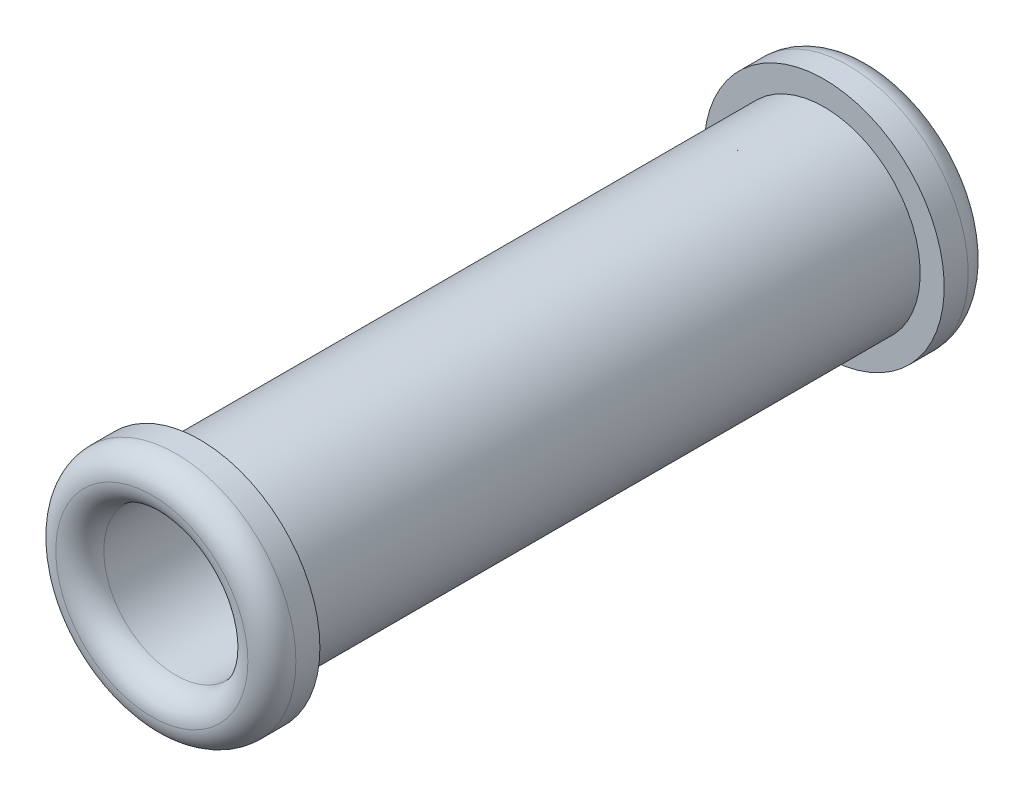
SolidWorks part; units mm, degrees
ref_plane "Front Plane" through (0, 0, 0) normal (0, 0, 1) x (1, 0, 0)
ref_plane "Top Plane" through (0, 0, 0) normal (0, 1, 0) x (1, 0, 0)
ref_plane "Right Plane" through (0, 0, 0) normal (1, 0, 0) x (0, 0, -1)
sketch "Sketch1" plane through (0, 0, 0) normal (0, 0, 1) x (1, 0, 0)
  circle A0 centre (0, 0) radius 1
  dimension "D1" = 2
extrude "Boss-Extrude1" add sketch "Sketch1" along normal blind 6.5
sketch "Sketch2" plane through (0, 0, 6.5) normal (0, 0, 1) x (1, 0, 0)
  circle A0 centre (0, 0) radius 1.25
  dimension "D1" = 2.5
extrude "Boss-Extrude2" add sketch "Sketch2" along normal blind 0.5
sketch "Sketch3" plane through (0, 0, 0) normal (0, 0, -1) x (-1, 0, 0)
  circle A0 centre (0, 0) radius 1.25
  dimension "D1" = 2.5
extrude "Boss-Extrude3" add sketch "Sketch3" along normal blind 0.5
sketch "Sketch4" plane through (0, 0, 7) normal (0, 0, 1) x (1, 0, 0)
  circle A0 centre (0, 0) radius 0.75
  dimension "D1" = 1.5
extrude "Cut-Extrude1" cut sketch "Sketch4" against normal blind 10.5
fillet "Fillet1" radius 0.25 4 edges at (-0.75, 0, -0.5) (-1.25, 0, -0.5) (0.75, 0, 7) (1.25, 0, 7)
